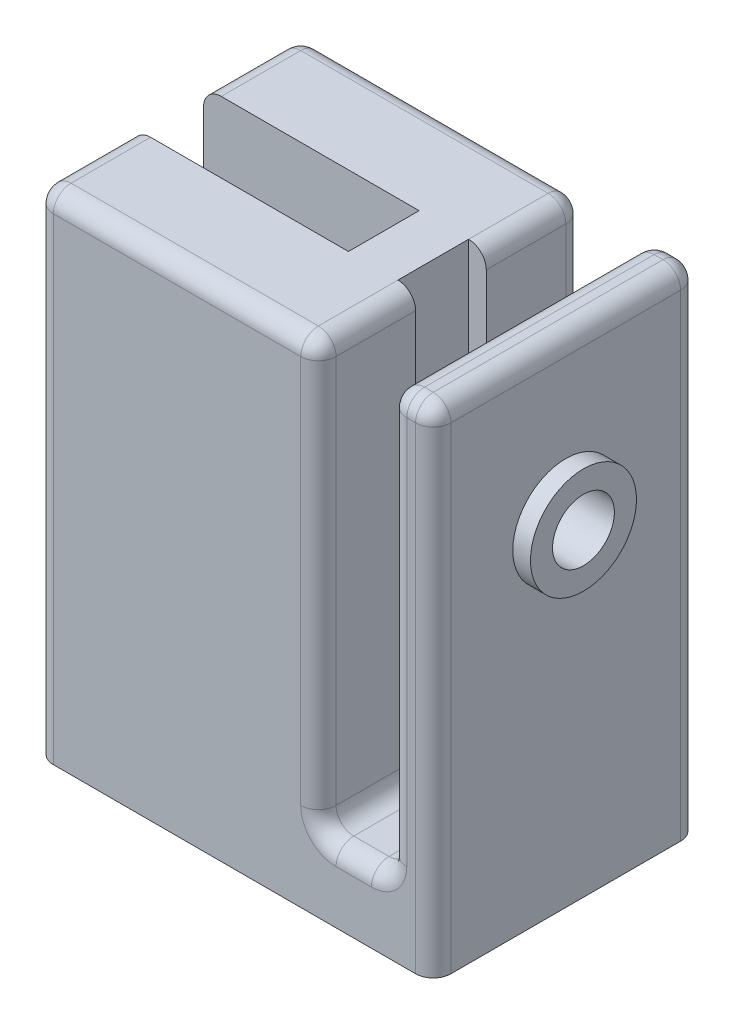
SolidWorks part; units mm, degrees
ref_plane "Plan de face" through (0, 0, 0) normal (0, 0, 1) x (1, 0, 0)
ref_plane "Plan de dessus" through (0, 0, 0) normal (0, 1, 0) x (1, 0, 0)
ref_plane "Plan de droite" through (0, 0, 0) normal (1, 0, 0) x (0, 0, -1)
sketch "Esquisse1" plane through (0, 0, 0) normal (0, 1, 0) x (1, 0, 0)
  line L0 (0, 0) -> (0, 15) construction
  line L1 (0, 0) -> (66, 0) construction
  line L2 (10.5, 15) -> (10.5, -15) construction
  line L3 (-12, -15) -> (33, -15)
  line L4 (-12, -15) -> (-12, 15)
  line L5 (-12, 15) -> (33, 15)
  line L6 (33, -15) -> (33, 15)
  point P8 (33, 0)
  dimension "D1" = 30
  dimension "D2" = 45
  dimension "D3" = 10.5
extrude "Boss.-Extru.1" add sketch "Esquisse1" along normal blind 8
sketch "Esquisse5" plane through (-12, 0, 0) normal (-1, 0, 0) x (0, 0, 1)
  line L0 (-15, 8) -> (-15, 56)
  line L1 (-15, 56) -> (15, 56)
  line L2 (15, 56) -> (15, 8)
  line L3 (-15, 8) -> (15, 8)
  dimension "D1" = 48
extrude "Boss.-Extru.3" add sketch "Esquisse5" against normal blind 32
sketch "Esquisse6" plane through (-12, 0, 0) normal (-1, 0, 0) x (0, 0, 1)
  line L0 (15, 8) -> (-15, 8) construction
  line L1 (15, 8) -> (-15, 8) construction
  line L2 (10.25, 48) -> (4, 48)
  line L3 (-10.25, 48) -> (-10.25, 8)
  line L4 (-10.25, 8) -> (10.25, 8)
  line L5 (10.25, 8) -> (10.25, 48)
  line L6 (0, 0) -> (0, 56) construction
  line L7 (-15, 0) -> (15, 0) construction
  line L8 (15, 56) -> (-15, 56) construction
  line L9 (-15, 28) -> (15, 28) construction
  line L10 (-15, 56) -> (-15, 0) construction
  line L11 (15, 56) -> (15, 0) construction
  line L12 (4, 48) -> (4, 56)
  line L13 (4, 56) -> (-4, 56)
  line L14 (-4, 56) -> (-4, 48)
  line L15 (-4, 48) -> (-10.25, 48)
  point P11 (0, 8)
  point P20 (0, 28)
  point P25 (0, 56)
  dimension "D1" = 20.5
  dimension "D2" = 8
  dimension "D3" = 40
extrude "Enlèv. mat.-Extru.1" cut sketch "Esquisse6" against normal blind 27 contours L2 L12 L13 L14 L15 L3 L4 L5
sketch "Esquisse7" plane through (-12, 0, 0) normal (-1, 0, 0) x (0, 0, 1)
  line L0 (0, 0) -> (0, 8) construction
  line L1 (-15, 0) -> (15, 0) construction
  line L2 (-10.25, 8) -> (10.25, 8) construction
  line L3 (-5, 4) -> (5, 4) construction
  circle A0 centre (-5, 4) radius 1.3509
  circle A1 centre (5, 4) radius 1.3509
  dimension "D1" = 10
  dimension "D2" = 4
sketch "Esquisse14" plane through (0, 56, 0) normal (0, 1, 0) x (1, 0, 0)
  line L1 (18, 4) -> (24, 4)
  line L3 (20, -15) -> (20, 15) construction
  line L4 (24, 4) -> (24, -4)
  line L5 (15, -4) -> (-12, -4) construction
  line L6 (20, -4) -> (18, -4) construction
  line L7 (20, -4) -> (20, 4) construction
  line L8 (20, 4) -> (18, 4) construction
  line L9 (18, -4) -> (18, 4)
  line L10 (15, 4) -> (-12, 4) construction
  line L11 (24, -4) -> (18, -4)
  dimension "D1" = 2
  dimension "D2" = 6
extrude "Enlèv. mat.-Extru.2" cut sketch "Esquisse14" against normal through all
hole_wizard "Dégagement M31" positions "Esquisse12" profile "Esquisse13" hole size "M3" standard "ISO"
sketch "Esquisse12" plane through (-12, 0, 0) normal (-1, 0, 0) x (0, 0, 1)
  point P0 (5, 4)
  point P3 (-5, 4)
sketch "Esquisse13" plane through (-12, 4, 5) normal (0, 1, 0) x (0, 0, 1)
  line L0 (0, 0) -> (0, 7.9614)
  line L1 (0, 7.9614) -> (1.6, 7)
  line L2 (1.6, 7) -> (1.6, 0)
  line L5 (1.6, 0) -> (0, 0)
  line L10 (0, 7.9614) -> (-1.6, 7) construction
  line L11 (0, -6.35) -> (0, 107.95) construction
  dimension "Diamètre du perçage" = 3.2
  dimension "Profondeur du perçage" = 7
  dimension "Angle de pointe" = 118
sketch "Esquisse16" plane through (33, 0, 0) normal (1, 0, 0) x (0, 0, -1)
  line L0 (0, 0) -> (0, 56) construction
  line L1 (-15, 0) -> (15, 0) construction
  line L2 (4, 56) -> (-4, 56) construction
  line L3 (-15, 8) -> (15, 8) construction
  line L4 (-15, 8) -> (-15, 56) construction
  line L5 (15, 56) -> (15, 8) construction
  line L6 (-15, 56) -> (-4, 56) construction
  line L7 (-15, 8) -> (15, 8)
  line L8 (-15, 8) -> (-15, 56)
  line L9 (15, 56) -> (15, 8)
  line L10 (-15, 56) -> (15, 56)
  circle A0 centre (0, 38) radius 3.5
  dimension "D1" = 7
  dimension "D2" = 18
extrude "Boss.-Extru.4" add sketch "Esquisse16" against normal blind 5
fillet "Congé1" radius 2 23 edges at (24, 8, -15) (24, 8, 15) (33, 28, 15) (33, 28, -15) (-12, 28, 15) (-12, 28, -15) (-12, 56, -9.5) (-12, 56, 9.5) (20, 8, -9.5) (20, 8, 9.5) (4, 56, -15) (20, 32, -15) (4, 56, 15) (20, 32, 15) (20, 56, -9.5) (20, 56, 9.5) (30.5, 56, 15) (28, 56, 0) (30.5, 56, -15) (33, 56, 0) (28, 8, 0) (28, 32, -15) (28, 32, 15)
sketch "Esquisse17" plane through (28, 0, 0) normal (-1, 0, 0) x (0, 0, 1)
  line L0 (0, 0) -> (0, 56) construction
  line L1 (-13, 56) -> (13, 56) construction
  line L3 (-5, 33) -> (5, 33)
  line L4 (-5, 33) -> (-5, 43)
  line L5 (-5, 43) -> (5, 43)
  line L6 (5, 33) -> (5, 43)
  line L7 (-5, 33) -> (5, 43) construction
  line L8 (-5, 43) -> (5, 33) construction
  circle A0 centre (0, 38) radius 3.5 construction
  circle A1 centre (0, 38) radius 3.5 construction
  dimension "D1" = 10
extrude "Enlèv. mat.-Extru.3" cut sketch "Esquisse17" against normal blind 2
sketch "Esquisse18" plane through (33, 0, 0) normal (1, 0, 0) x (0, 0, -1)
  line L0 (0, 0) -> (0, 54) construction
  line L1 (-13, 0) -> (13, 0) construction
  line L2 (13, 54) -> (-13, 54) construction
  circle A0 centre (0, 38) radius 3.5 construction
  circle A1 centre (0, 38) radius 3.5
  circle A2 centre (0, 38) radius 6
  dimension "D1" = 12
extrude "Boss.-Extru.5" add sketch "Esquisse18" along normal blind 2
ref_axis "Axe2" through (0, 58.8, 0) along (0, -1, 0)
sketch "Esquisse21" plane through (0, 8, 0) normal (0, 1, 0) x (1, 0, 0)
  line L0 (0, 0) -> (0, 23.8533) construction
  line L1 (-7.5, 0) -> (7.5, 0) construction
  point P6 (0, 0)
  dimension "D1" = 15
hole_wizard "Fraisage pour vis à tête fraisée M31" positions "Esquisse22" profile "Esquisse23" countersink size "M3" standard "ISO" end condition through all
sketch "Esquisse22" plane through (0, 8, 0) normal (0, 1, 0) x (1, 0, 0)
  point P0 (-7.5, 0)
  point P3 (7.5, 0)
sketch "Esquisse23" plane through (-7.5, 8, 0) normal (1, 0, 0) x (0, 0, 1)
  line L0 (0, 0) -> (0, 8)
  line L1 (0, 8) -> (1.7, 8)
  line L2 (1.7, 8) -> (1.7, 1.45)
  line L3 (1.7, 1.45) -> (3.15, 0)
  line L5 (3.15, 0) -> (0, 0)
  line L6 (-1.7, 1.45) -> (-3.15, 0) construction
  line L11 (0, -6.35) -> (0, 107.95) construction
  dimension "Diamètre du perçage jusqu'au prochain" = 3.4
  dimension "Profondeur du perçage jusqu'au prochain" = 8
  dimension "Diamètre du fraisage entrant" = 6.3
  dimension "Angle du fraisage entrant" = 90
sketch "Esquisse24" plane through (15, 0, 0) normal (-1, 0, 0) x (0, 0, 1)
  line L0 (0, 0) -> (0, 79.3544) construction
  line L1 (4, 56) -> (-4, 56) construction
  line L2 (-4, 56) -> (-4, 48) construction
  line L3 (4, 48) -> (4, 56) construction
  line L4 (4, 56) -> (-4, 56)
  line L5 (-4, 56) -> (-4, 48)
  line L6 (4, 48) -> (4, 56)
  line L7 (4, 48) -> (-4, 48)
extrude "Boss.-Extru.6" add sketch "Esquisse24" along normal blind 2.6
ref_axis "Axe3" through (-79.077, 38, 0) along (1, 0, 0)
